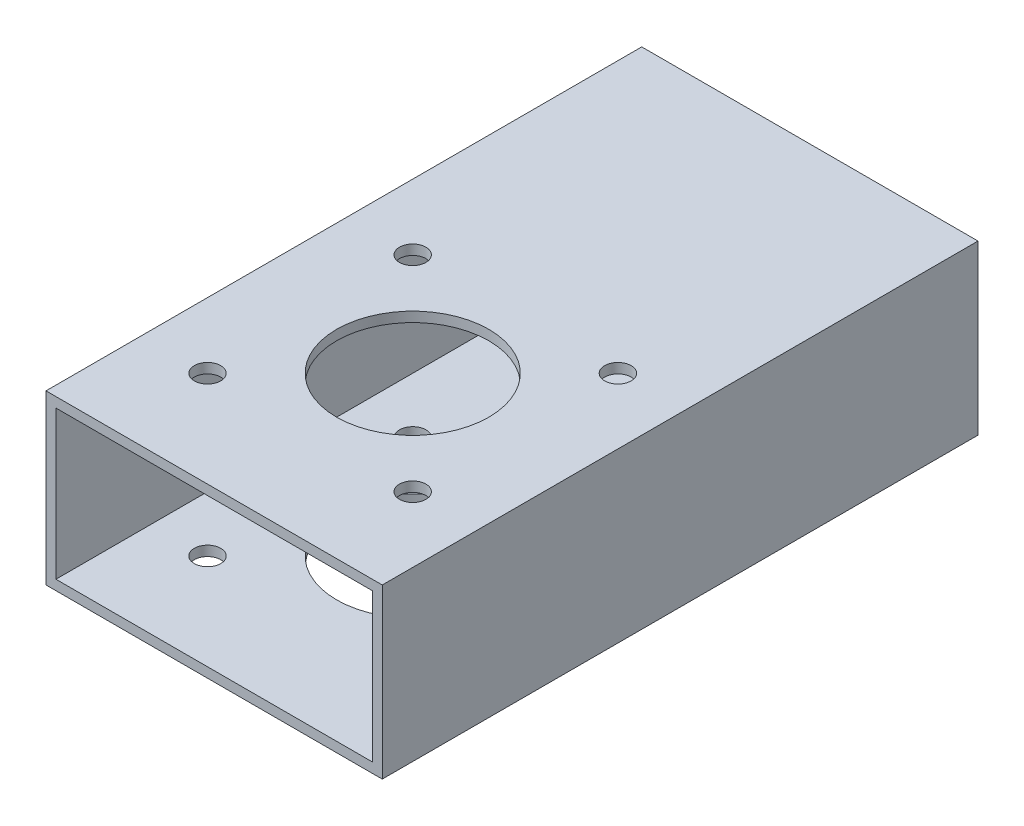
SolidWorks part; units mm, degrees
material "AISI 1015 Acero estirado en frío (SS)"
ref_plane "Alzado" through (0, 0, 0) normal (0, 0, 1) x (1, 0, 0)
ref_plane "Planta" through (0, 0, 0) normal (0, 1, 0) x (1, 0, 0)
ref_plane "Vista lateral" through (0, 0, 0) normal (1, 0, 0) x (0, 0, -1)
sketch "Croquis1" plane through (0, 0, 0) normal (0, 0, 1) x (1, 0, 0)
  line L0 (-23.9, 11.2) -> (23.9, 11.2)
  line L1 (-25.4, -12.7) -> (25.4, -12.7)
  line L2 (-25.4, -12.7) -> (-25.4, 12.7)
  line L3 (-25.4, 12.7) -> (25.4, 12.7)
  line L4 (25.4, -12.7) -> (25.4, 12.7)
  line L5 (-25.4, -12.7) -> (25.4, 12.7) construction
  line L6 (-25.4, 12.7) -> (25.4, -12.7) construction
  line L7 (23.9, -11.2) -> (23.9, 11.2)
  line L8 (-23.9, -11.2) -> (23.9, -11.2)
  line L9 (-23.9, -11.2) -> (-23.9, 11.2)
  point P0 (0, 0)
  dimension "D1" = 25.4
  dimension "D2" = 50.8
  dimension "D3" = 1.5
extrude "Saliente-Extruir1" add sketch "Croquis1" along normal blind 90
ref_plane "Plano1" through (0, -12.7, 0) normal (0, -1, 0) x (-1, 0, 0)
sketch "Croquis2" plane through (0, -12.7, 0) normal (0, -1, 0) x (-1, 0, 0)
  line L0 (0, -90) -> (0, 0) construction
  line L1 (25.4, -90) -> (-25.4, -90) construction
  line L2 (25.4, 0) -> (-25.4, 0) construction
  line L3 (-25.4, -60) -> (25.4, -60) construction
  line L4 (-25.4, -90) -> (-25.4, 0) construction
  line L5 (25.4, -90) -> (25.4, 0) construction
  circle A0 centre (0, -60) radius 11.5
  circle A1 centre (15.5, -75.5) radius 2
  circle A2 centre (-15.5, -75.5) radius 2
  circle A3 centre (-15.5, -44.5) radius 2
  circle A4 centre (15.5, -44.5) radius 2
  dimension "D2" = 23
  dimension "D5" = 4
  dimension "D1" = 30
  dimension "D3" = 15.5
  dimension "D4" = 15.5
extrude "Cortar-Extruir1" cut sketch "Croquis2" against normal blind 26
